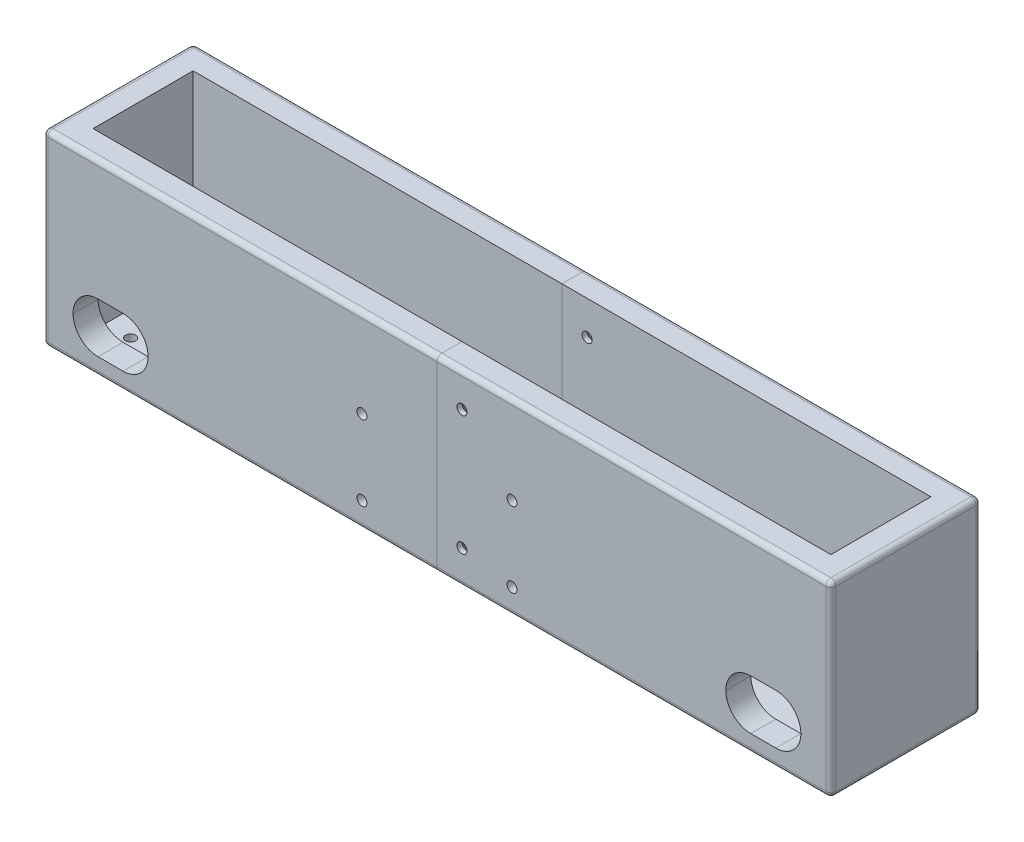
SolidWorks part; units mm, degrees
ref_plane "Front Plane" through (0, 0, 0) normal (0, 0, 1) x (1, 0, 0)
ref_plane "Top Plane" through (0, 0, 0) normal (0, 1, 0) x (1, 0, 0)
ref_plane "Right Plane" through (0, 0, 0) normal (1, 0, 0) x (0, 0, -1)
sketch "Sketch1" plane through (0, 0, 0) normal (0, 1, 0) x (1, 0, 0)
  line L1 (157.5, 30) -> (-157.5, 30)
  line L2 (157.5, 30) -> (157.5, -30)
  line L3 (157.5, -30) -> (-157.5, -30)
  line L4 (-157.5, 30) -> (-157.5, -30)
  line L5 (157.5, 30) -> (-157.5, -30) construction
  line L6 (157.5, -30) -> (-157.5, 30) construction
  point P0 (0, 0)
  dimension "D1" = 315
  dimension "D2" = 60
extrude "Boss-Extrude1" add sketch "Sketch1" along normal blind 75
sketch "Sketch2" plane through (0, 75, 0) normal (0, 1, 0) x (1, 0, 0)
  line L0 (-157.5, 30) -> (-157.5, -30) construction
  line L1 (-147.5, 20) -> (147.5, 20)
  line L2 (-147.5, 20) -> (-147.5, -20)
  line L3 (-147.5, -20) -> (147.5, -20)
  line L4 (147.5, 20) -> (147.5, -20)
  line L5 (-147.5, 20) -> (147.5, -20) construction
  line L6 (-147.5, -20) -> (147.5, 20) construction
  line L8 (157.5, 30) -> (-157.5, 30) construction
  point P1 (0, 0)
  dimension "D1" = 10
  dimension "D2" = 10
extrude "Cut-Extrude1" cut sketch "Sketch2" against normal blind 70
fillet "Fillet1" radius 2 4 edges at (157.5, 0, 0) (157.5, 75, 0) (-157.5, 0, 0) (-157.5, 75, 0)
fillet "Fillet2" radius 2 16 edges at (-156.9142, 74.4142, -30) (0, 75, -30) (156.9142, 74.4142, -30) (157.5, 37.5, -30) (156.9142, 0.5858, -30) (0, 0, -30) (-156.9142, 0.5858, -30) (-156.9142, 74.4142, 30) (0, 75, 30) (156.9142, 74.4142, 30) (157.5, 37.5, 30) (156.9142, 0.5858, 30) (0, 0, 30) (-156.9142, 0.5858, 30) (-157.5, 37.5, -30) (-157.5, 37.5, 30)
split "Split1" trim tools "Right Plane" bodies to split 102 resulting bodies 104 105
sketch "Sketch4" plane through (0, 0, 30) normal (0, 0, 1) x (1, 0, 0)
  line L0 (0, 0) -> (0, 85.0467) construction
  line L3 (0, 37.5) -> (232.745, 37.5) construction
  line L4 (155.5, 0) -> (0, 0) construction
  circle A0 centre (10, 61.5) radius 2
  circle A1 centre (10, 13.5) radius 2
  dimension "D1" = 4
  dimension "D2" = 20
  dimension "D3" = 37.5
  dimension "D4" = 24
extrude "Cut-Extrude3" cut sketch "Sketch4" against normal blind 70
sketch "Sketch5" plane through (0, 0, 0) normal (-1, 0, 0) x (0, 0, 1)
  line L8 (-28, 2) -> (-22, 2)
  line L9 (22, 2) -> (28, 2)
  line L16 (-28, 73) -> (-28, 2)
  line L17 (-28, 2) -> (28, 2)
  line L18 (28, 2) -> (28, 73)
  line L19 (28, 73) -> (22, 73)
  line L20 (22, 73) -> (22, 3)
  line L21 (22, 3) -> (-22, 3)
  line L22 (-22, 3) -> (-22, 73)
  line L23 (-22, 73) -> (-28, 73)
  line L24 (-28, 73) -> (-28, 2)
  line L26 (28, 2) -> (28, 73)
  line L27 (28, 73) -> (22, 73)
  line L28 (22, 73) -> (22, 2)
  line L30 (-22, 2) -> (-22, 73)
  line L31 (-22, 73) -> (-28, 73)
  dimension "D1" = 2
extrude "Cut-Extrude4" cut sketch "Sketch5" against normal blind 20
sketch "Sketch6" plane through (0, 0, 0) normal (1, 0, 0) x (0, 0, -1)
  line L8 (-27.6, 2.4) -> (-22.4, 2.4)
  line L9 (22.4, 2.4) -> (27.6, 2.4)
  line L16 (27.6, 72.6) -> (22.4, 72.6)
  line L17 (22.4, 72.6) -> (22.4, 2.6)
  line L18 (22.4, 2.6) -> (-22.4, 2.6)
  line L19 (-22.4, 2.6) -> (-22.4, 72.6)
  line L20 (-22.4, 72.6) -> (-27.6, 72.6)
  line L21 (-27.6, 72.6) -> (-27.6, 2.4)
  line L22 (-27.6, 2.4) -> (27.6, 2.4)
  line L23 (27.6, 2.4) -> (27.6, 72.6)
  line L24 (27.6, 72.6) -> (22.4, 72.6)
  line L25 (22.4, 72.6) -> (22.4, 2.4)
  line L27 (-22.4, 2.4) -> (-22.4, 72.6)
  line L28 (-22.4, 72.6) -> (-27.6, 72.6)
  line L29 (-27.6, 72.6) -> (-27.6, 2.4)
  line L31 (27.6, 2.4) -> (27.6, 72.6)
  dimension "D1" = 2.4
extrude "Boss-Extrude2" add sketch "Sketch6" along normal blind 20
sketch "Sketch7" plane through (0, 0, 27.6) normal (0, 0, 1) x (1, 0, 0)
  line L0 (20, 72.6) -> (20, 2.4) construction
  line L1 (20, 37.5) -> (52.7601, 37.5) construction
  circle A0 centre (10, 61.5) radius 2
  circle A1 centre (10, 13.5) radius 2
  dimension "D1" = 4
  dimension "D2" = 10
  dimension "D3" = 24
extrude "Cut-Extrude5" cut sketch "Sketch7" against normal blind 77
sketch "Sketch8" plane through (0, 5, 0) normal (0, 1, 0) x (1, 0, 0)
  line L0 (0, 0) -> (200.9595, 0) construction
  line L1 (0, 0) -> (-175.0415, 0) construction
  line L2 (157.5, 28) -> (157.5, -28) construction
  line L3 (0, -33) -> (0, 33) construction
  circle A0 centre (137.5, 15) radius 2
  circle A1 centre (137.5, -15) radius 2
  circle A2 centre (-137.5, -15) radius 2
  circle A3 centre (-137.5, 15) radius 2
  dimension "D1" = 4
  dimension "D2" = 20
  dimension "D3" = 30
extrude "Cut-Extrude6" cut sketch "Sketch8" against normal through all
sketch "Sketch11" plane through (0, 0, 30) normal (0, 0, 1) x (1, 0, 0)
  line L0 (0, 0) -> (0, 97.4561) construction
  line L1 (-155.5, 2) -> (0, 2) construction
  circle A0 centre (-30, 10) radius 2
  circle A1 centre (-30, 40) radius 2
  circle A2 centre (30, 10) radius 2
  circle A3 centre (30, 40) radius 2
  dimension "D1" = 4
  dimension "D5" = 4
  dimension "D2" = 8
  dimension "D3" = 30
  dimension "D4" = 30
extrude "Cut-Extrude7" cut sketch "Sketch11" against normal blind 10
sketch "Sketch13" plane through (0, 0, 30) normal (0, 0, 1) x (1, 0, 0)
  line L0 (0, 2) -> (155.5, 2) construction
  line L1 (115.5, 27) -> (145.5, 27)
  line L2 (115.5, 27) -> (115.5, 7)
  line L3 (115.5, 7) -> (145.5, 7)
  line L4 (145.5, 27) -> (145.5, 7)
  line L5 (155.5, 2) -> (155.5, 73) construction
  line L6 (0, 73) -> (0, 2) construction
  line L7 (-145.5, 27) -> (-145.5, 7)
  line L8 (-115.5, 7) -> (-145.5, 7)
  line L9 (-115.5, 27) -> (-115.5, 7)
  line L10 (-115.5, 27) -> (-145.5, 27)
  dimension "D1" = 20
  dimension "D2" = 30
  dimension "D3" = 5
  dimension "D4" = 10
extrude "Cut-Extrude9" cut sketch "Sketch13" against normal blind 10
other "Save Bodies2"
fillet "Fillet4" radius 10 4 edges at (-115.5, 7, 25) (-115.5, 27, 25) (-145.5, 27, 25) (-145.5, 7, 25)
fillet "Fillet5" radius 10 4 edges at (145.5, 27, 25) (115.5, 7, 25) (145.5, 7, 25) (115.5, 27, 25)
other "Save Bodies3"
other "Save Bodies4"
